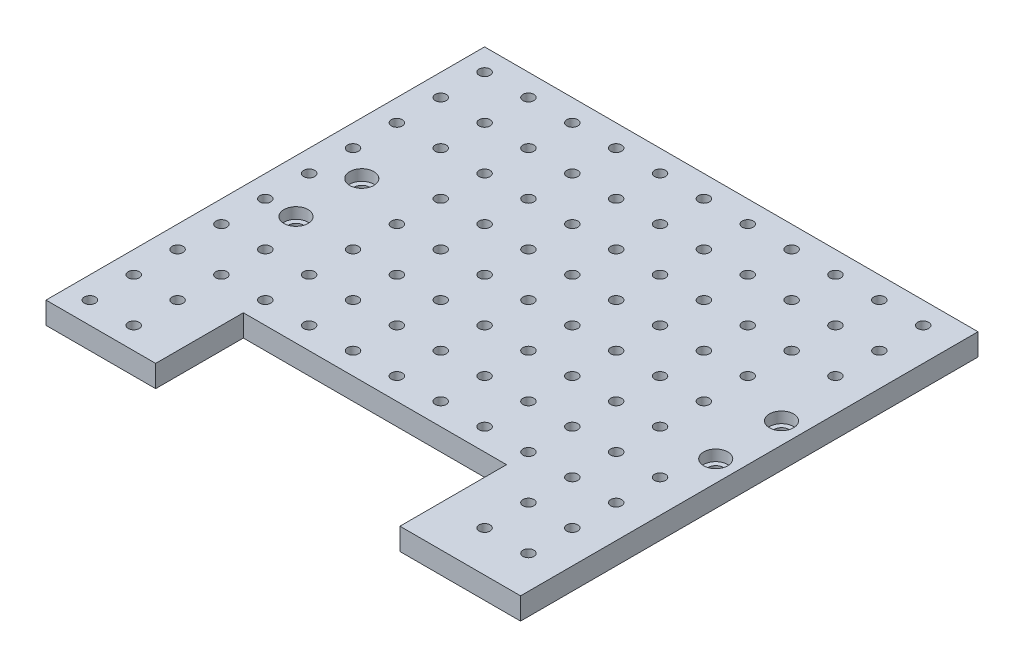
SolidWorks part; units mm, degrees
ref_plane "Front Plane" through (0, 0, 0) normal (0, 0, 1) x (1, 0, 0)
ref_plane "Top Plane" through (0, 0, 0) normal (0, 1, 0) x (1, 0, 0)
ref_plane "Right Plane" through (0, 0, 0) normal (1, 0, 0) x (0, 0, -1)
sketch "Sketch1" plane through (0, 0, 0) normal (0, 1, 0) x (1, 0, 0)
  line L1 (63.5, 0) -> (215.9, 0)
  line L2 (0, 0) -> (0, 203.2)
  line L3 (0, 203.2) -> (285.75, 203.2)
  line L4 (285.75, 0) -> (285.75, 203.2)
  line L6 (0, 0) -> (0, -50.8)
  line L7 (0, -50.8) -> (63.5, -50.8)
  line L8 (63.5, 0) -> (63.5, -50.8)
  line L10 (285.75, 0) -> (285.75, -61.722)
  line L11 (285.75, -61.722) -> (215.9, -61.722)
  line L12 (215.9, 0) -> (215.9, -61.722)
  circle A0 centre (12.7, 190.5) radius 3.175
  circle A1 centre (38.1, 190.5) radius 3.175
  circle A2 centre (63.5, 190.5) radius 3.175
  circle A3 centre (88.9, 190.5) radius 3.175
  circle A4 centre (114.3, 190.5) radius 3.175
  circle A5 centre (139.7, 190.5) radius 3.175
  circle A6 centre (165.1, 190.5) radius 3.175
  circle A7 centre (190.5, 190.5) radius 3.175
  circle A8 centre (215.9, 190.5) radius 3.175
  circle A9 centre (241.3, 190.5) radius 3.175
  circle A10 centre (266.7, 190.5) radius 3.175
  circle A11 centre (38.1, 165.1) radius 3.175
  circle A12 centre (63.5, 165.1) radius 3.175
  circle A13 centre (88.9, 165.1) radius 3.175
  circle A14 centre (114.3, 165.1) radius 3.175
  circle A15 centre (139.7, 165.1) radius 3.175
  circle A16 centre (165.1, 165.1) radius 3.175
  circle A17 centre (190.5, 165.1) radius 3.175
  circle A18 centre (215.9, 165.1) radius 3.175
  circle A19 centre (241.3, 165.1) radius 3.175
  circle A20 centre (266.7, 165.1) radius 3.175
  circle A21 centre (38.1, 139.7) radius 3.175
  circle A22 centre (63.5, 139.7) radius 3.175
  circle A23 centre (88.9, 139.7) radius 3.175
  circle A24 centre (114.3, 139.7) radius 3.175
  circle A25 centre (139.7, 139.7) radius 3.175
  circle A26 centre (165.1, 139.7) radius 3.175
  circle A27 centre (190.5, 139.7) radius 3.175
  circle A28 centre (215.9, 139.7) radius 3.175
  circle A29 centre (241.3, 139.7) radius 3.175
  circle A30 centre (266.7, 139.7) radius 3.175
  circle A32 centre (63.5, 114.3) radius 3.175
  circle A33 centre (88.9, 114.3) radius 3.175
  circle A34 centre (114.3, 114.3) radius 3.175
  circle A35 centre (139.7, 114.3) radius 3.175
  circle A36 centre (165.1, 114.3) radius 3.175
  circle A37 centre (190.5, 114.3) radius 3.175
  circle A38 centre (215.9, 114.3) radius 3.175
  circle A39 centre (241.3, 114.3) radius 3.175
  circle A42 centre (63.5, 88.9) radius 3.175
  circle A43 centre (88.9, 88.9) radius 3.175
  circle A44 centre (114.3, 88.9) radius 3.175
  circle A45 centre (139.7, 88.9) radius 3.175
  circle A46 centre (165.1, 88.9) radius 3.175
  circle A47 centre (190.5, 88.9) radius 3.175
  circle A48 centre (215.9, 88.9) radius 3.175
  circle A49 centre (241.3, 88.9) radius 3.175
  circle A52 centre (63.5, 63.5) radius 3.175
  circle A53 centre (88.9, 63.5) radius 3.175
  circle A54 centre (114.3, 63.5) radius 3.175
  circle A55 centre (139.7, 63.5) radius 3.175
  circle A56 centre (165.1, 63.5) radius 3.175
  circle A57 centre (190.5, 63.5) radius 3.175
  circle A58 centre (215.9, 63.5) radius 3.175
  circle A59 centre (241.3, 63.5) radius 3.175
  circle A61 centre (38.1, 38.1) radius 3.175
  circle A62 centre (63.5, 38.1) radius 3.175
  circle A63 centre (88.9, 38.1) radius 3.175
  circle A64 centre (114.3, 38.1) radius 3.175
  circle A65 centre (139.7, 38.1) radius 3.175
  circle A66 centre (165.1, 38.1) radius 3.175
  circle A67 centre (190.5, 38.1) radius 3.175
  circle A68 centre (215.9, 38.1) radius 3.175
  circle A69 centre (241.3, 38.1) radius 3.175
  circle A70 centre (266.7, 38.1) radius 3.175
  circle A71 centre (38.1, 12.7) radius 3.175
  circle A72 centre (63.5, 12.7) radius 3.175
  circle A73 centre (88.9, 12.7) radius 3.175
  circle A74 centre (114.3, 12.7) radius 3.175
  circle A75 centre (139.7, 12.7) radius 3.175
  circle A76 centre (165.1, 12.7) radius 3.175
  circle A77 centre (190.5, 12.7) radius 3.175
  circle A78 centre (215.9, 12.7) radius 3.175
  circle A79 centre (241.3, 12.7) radius 3.175
  circle A80 centre (266.7, 12.7) radius 3.175
  circle A81 centre (38.1, -12.7) radius 3.175
  circle A89 centre (241.3, -12.7) radius 3.175
  circle A90 centre (266.7, -12.7) radius 3.175
  circle A91 centre (38.1, -38.1) radius 3.175
  circle A99 centre (241.3, -38.1) radius 3.175
  circle A100 centre (266.7, -38.1) radius 3.175
  circle A101 centre (12.7, 165.1) radius 3.175
  circle A102 centre (12.7, 139.7) radius 3.175
  circle A103 centre (12.7, 114.3) radius 3.175
  circle A104 centre (12.7, 88.9) radius 3.175
  circle A105 centre (12.7, 63.5) radius 3.175
  circle A106 centre (12.7, 38.1) radius 3.175
  circle A107 centre (12.7, 12.7) radius 3.175
  circle A108 centre (12.7, -12.7) radius 3.175
  circle A109 centre (12.7, -38.1) radius 3.175
  circle A110 centre (88.9, -12.7) radius 3.175 [skipped]
  circle A111 centre (114.3, -12.7) radius 3.175 [skipped]
  circle A112 centre (139.7, -12.7) radius 3.175 [skipped]
  circle A113 centre (165.1, -12.7) radius 3.175 [skipped]
  circle A114 centre (190.5, -12.7) radius 3.175 [skipped]
  arc A115 (215.9, -15.875) -> (215.9, -9.525) centre (215.9, -12.7) ccw [skipped]
  arc A116 (215.9, -34.925) -> (215.9, -41.275) centre (215.9, -38.1) ccw [skipped]
  circle A117 centre (190.5, -38.1) radius 3.175 [skipped]
  circle A118 centre (165.1, -38.1) radius 3.175 [skipped]
  circle A119 centre (139.7, -38.1) radius 3.175 [skipped]
  circle A120 centre (114.3, -38.1) radius 3.175 [skipped]
  circle A121 centre (88.9, -38.1) radius 3.175 [skipped]
  arc A122 (63.5, -34.925) -> (63.5, -41.275) centre (63.5, -38.1) ccw [skipped]
  arc A123 (63.5, -9.525) -> (63.5, -15.875) centre (63.5, -12.7) ccw [skipped]
  circle A124 centre (38.1, 114.3) radius 3.175 [skipped]
  circle A125 centre (38.1, 88.9) radius 3.175 [skipped]
  circle A126 centre (266.7, 114.3) radius 3.175 [skipped]
  circle A127 centre (266.7, 88.9) radius 3.175 [skipped]
  circle A128 centre (266.7, 63.5) radius 3.175 [skipped]
  circle A129 centre (38.1, 63.5) radius 3.175 [skipped]
  dimension "D9" = 6.35
  dimension "D1" = 203.2
  dimension "D2" = 285.75
  dimension "D3" = 50.8
  dimension "D4" = 63.5
  dimension "D5" = 61.722
  dimension "D6" = 69.85
  dimension "D7" = 12.7
  dimension "D8" = 12.7
  dimension "D10" = 11
  dimension "D11" = 10
extrude "Boss-Extrude1" add sketch "Sketch1" along normal blind 12.7
sketch "Sketch2" plane through (0, 12.7, 0) normal (0, 1, 0) x (1, 0, 0)
  line L0 (0, 203.2) -> (0, -50.8) construction
  line L1 (285.75, -61.722) -> (285.75, 203.2) construction
  line L2 (285.75, 203.2) -> (0, 203.2) construction
  circle A0 centre (30.48, 101.6) radius 4.191
  circle A1 centre (30.48, 101.6) radius 6.985
  circle A2 centre (30.48, 63.5) radius 4.191
  circle A3 centre (30.48, 63.5) radius 6.985
  circle A4 centre (273.558, 101.6) radius 4.191
  circle A5 centre (273.558, 101.6) radius 6.985
  circle A6 centre (273.558, 63.5) radius 4.191
  circle A7 centre (273.558, 63.5) radius 6.985
  point P18 (203.4898, 214.0158)
  point P19 (0, 0)
  dimension "D1" = 8.382
  dimension "D2" = 13.97
  dimension "D3" = 38.1
  dimension "D4" = 38.1
  dimension "D5" = 30.48
  dimension "D6" = 12.192
  dimension "D7" = 101.6
extrude "Cut-Extrude1" cut sketch "Sketch2" along direction (0, 1, 0) on the side against the normal offset from surface (6.35 mm away) 6.35 contours A3 | A1 | A5 | A7 up to face at (12.7, 12.7, 15.875)
extrude "Cut-Extrude2" cut sketch "Sketch2<3>" against normal offset from surface (12.7 mm away) 12.7 contours A4 | A2 | A0 | A6 region at (30.48, 12.7, -101.6) region at (30.48, 12.7, -63.5) region at (273.558, 12.7, -101.6) up to face at (273.558, 12.7, -56.515)
sketch "Sketch2<3>" plane through (0, 12.7, 0) normal (0, 1, 0) x (1, 0, 0) same geometry as "Sketch2"
